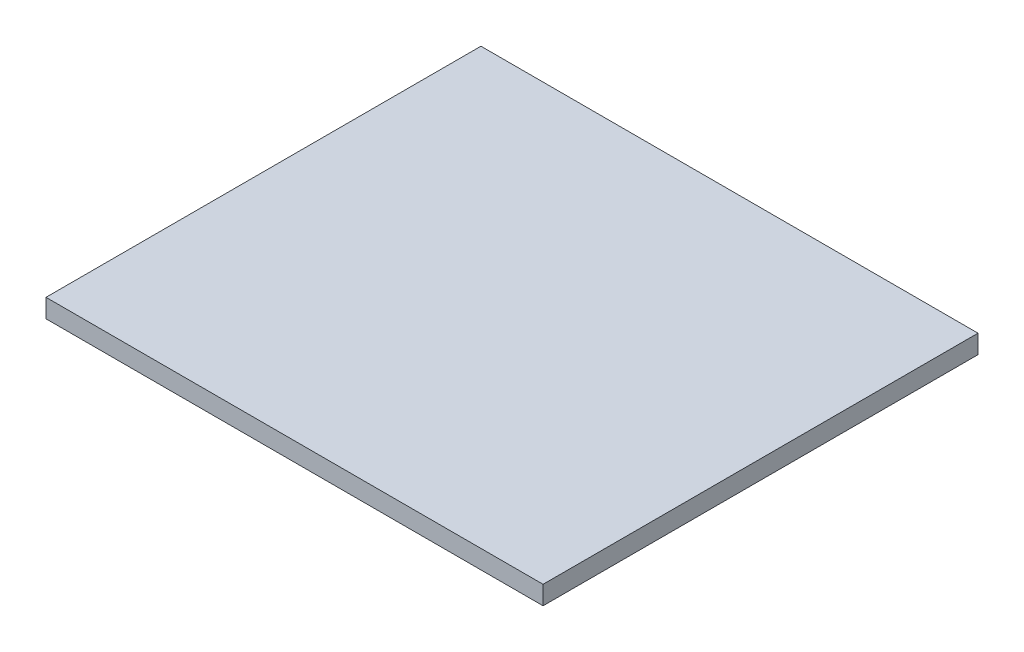
SolidWorks part; units mm, degrees
ref_plane "Front Plane" through (0, 0, 0) normal (0, 0, 1) x (1, 0, 0)
ref_plane "Top Plane" through (0, 0, 0) normal (0, 1, 0) x (1, 0, 0)
ref_plane "Right Plane" through (0, 0, 0) normal (1, 0, 0) x (0, 0, -1)
sketch "Sketch1" plane through (0, 0, 0) normal (0, 1, 0) x (1, 0, 0)
  line L1 (-20, 17.5) -> (20, 17.5)
  line L2 (-20, 17.5) -> (-20, -17.5)
  line L3 (-20, -17.5) -> (20, -17.5)
  line L4 (20, 17.5) -> (20, -17.5)
  line L5 (-20, 17.5) -> (20, -17.5) construction
  line L6 (-20, -17.5) -> (20, 17.5) construction
  point P0 (0, 0)
  dimension "D1" = 35
  dimension "D2" = 40
extrude "Boss-Extrude1" add sketch "Sketch1" along normal blind 1.5
